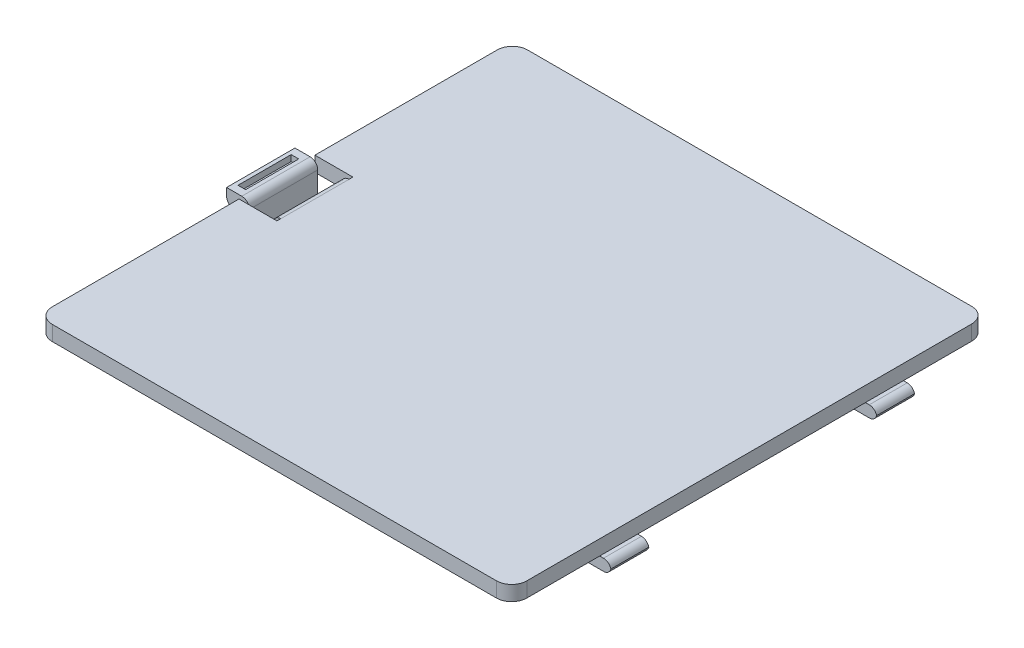
SolidWorks part; units mm, degrees
ref_plane "Front Plane" through (0, 0, 0) normal (0, 0, 1) x (1, 0, 0)
ref_plane "Top Plane" through (0, 0, 0) normal (0, 1, 0) x (1, 0, 0)
ref_plane "Right Plane" through (0, 0, 0) normal (1, 0, 0) x (0, 0, -1)
sketch "Sketch2" plane through (0, 0, 0) normal (0, 1, 0) x (1, 0, 0)
  line L0 (-98.1098, -87.5101) -> (50.4722, -87.5101)
  line L1 (-103.1898, -82.4301) -> (-103.1898, 66.3899)
  line L2 (-98.1098, 71.4699) -> (50.4722, 71.4699)
  line L3 (55.5522, -82.4301) -> (55.5522, 66.3899)
  arc A0 (-98.1098, -87.5101) -> (-103.1898, -82.4301) centre (-98.1098, -82.4301) cw
  arc A1 (50.4722, -87.5101) -> (55.5522, -82.4301) centre (50.4722, -82.4301) ccw
  arc A2 (50.4722, 71.4699) -> (55.5522, 66.3899) centre (50.4722, 66.3899) cw
  arc A3 (-103.1898, 66.3899) -> (-98.1098, 71.4699) centre (-98.1098, 66.3899) cw
  point P10 (55.5522, 71.4699)
  point P13 (-103.1898, 71.4699)
  dimension "D2" = 5.08
  dimension "D1" = 158.742
  dimension "D3" = 158.98
extrude "Boss-Extrude1" add sketch "Sketch2" along normal blind 5
sketch "Sketch8" plane through (0, 5, 0) normal (0, 1, 0) x (1, 0, 0)
  line L0 (-103.1898, 66.3899) -> (-103.1898, -82.4301) construction
  line L1 (-103.1898, 5.4299) -> (-90.4898, 5.4299)
  line L2 (-103.1898, 5.4299) -> (-103.1898, -19.9701)
  line L3 (-103.1898, -19.9701) -> (-90.4898, -19.9701)
  line L4 (-90.4898, 5.4299) -> (-90.4898, -19.9701)
  line L5 (50.4722, 71.4699) -> (-98.1098, 71.4699) construction
  dimension "D1" = 25.4
  dimension "D2" = 12.7
  dimension "D3" = 66.04
extrude "Cut-Extrude1" cut sketch "Sketch8" against normal blind 12.7
sketch "Sketch9" plane through (0, 0, 19.9701) normal (0, 0, -1) x (-1, 0, 0)
  line L0 (90.4898, 5) -> (90.4898, -9.5101)
  line L1 (93.0298, -12.0501) -> (100.9847, -12.0501)
  line L2 (103.5247, -9.5101) -> (103.5247, 5)
  line L3 (103.5247, 5) -> (100.9847, 5)
  line L4 (93.0298, 5) -> (93.0298, -6.9701)
  line L5 (95.5698, -9.5101) -> (98.4447, -9.5101)
  line L6 (100.9847, -6.9701) -> (100.9847, 5)
  line L7 (93.0298, 5) -> (90.4898, 5)
  arc A0 (90.4898, -9.5101) -> (93.0298, -12.0501) centre (93.0298, -9.5101) ccw
  arc A1 (100.9847, -12.0501) -> (103.5247, -9.5101) centre (100.9847, -9.5101) ccw
  arc A2 (98.4447, -9.5101) -> (100.9847, -6.9701) centre (98.4447, -6.9701) ccw
  arc A3 (93.0298, -6.9701) -> (95.5698, -9.5101) centre (95.5698, -6.9701) ccw
  dimension "D4" = 2.54
  dimension "D1" = 2.54
  dimension "D2" = 2.54
  dimension "D3" = 2.54
  dimension "D5" = 17.0501
extrude "Boss-Extrude6" add sketch "Sketch9" along normal blind 22.86 from offset 1.27
fillet "Fillet3" radius 2.54 1 edges at (-90.4898, 0, 7.2701)
sketch "Sketch12" plane through (-103.5247, 0, 0) normal (-1, 0, 0) x (0, 0, 1)
  line L0 (18.7001, 5) -> (18.7001, 0) construction
  line L1 (-4.1599, 5) -> (18.7001, 5)
  line L2 (-4.1599, 5) -> (-4.1599, -0.08)
  line L3 (-4.1599, -0.08) -> (18.7001, -0.08)
  line L4 (18.7001, 5) -> (18.7001, -0.08)
  dimension "D1" = 5.08
extrude "Boss-Extrude7" add sketch "Sketch12" along normal blind 5.08
fillet "Fillet8" radius 2.54 1 edges at (-100.9847, 5, 7.2701)
sketch "Sketch13" plane through (0, 5, 0) normal (0, 1, 0) x (1, 0, 0)
  line L0 (-108.6047, 4.1599) -> (-103.5247, 4.1599) construction
  line L1 (-104.7947, 1.6199) -> (-107.3347, 1.6199)
  line L2 (-104.7947, 1.6199) -> (-104.7947, -16.1601)
  line L3 (-104.7947, -16.1601) -> (-107.3347, -16.1601)
  line L4 (-107.3347, 1.6199) -> (-107.3347, -16.1601)
  line L5 (-108.6047, -18.7001) -> (-103.5247, -18.7001) construction
  line L6 (-103.5247, -18.7001) -> (-103.5247, 4.1599) construction
  line L8 (-108.6047, -18.7001) -> (-108.6047, 4.1599) construction
  dimension "D1" = 2.54
  dimension "D2" = 2.54
  dimension "D3" = 1.27
  dimension "D4" = 1.27
extrude "Cut-Extrude2" cut sketch "Sketch13" against normal blind 2.032
sketch "Sketch14" plane through (0, 0, -4.1599) normal (0, 0, -1) x (-1, 0, 0)
  line L0 (103.5247, -4.5768) -> (105.0487, -4.5768)
  line L1 (103.5247, -9.5101) -> (103.5247, -0.08) construction
  line L2 (105.0487, -4.5768) -> (103.5247, -7.3708)
  line L3 (103.5247, -7.3708) -> (103.5247, -4.5768)
  dimension "D1" = 1.524
  dimension "D2" = 2.794
extrude "Boss-Extrude8" add sketch "Sketch14" against normal up to surface (22.86 mm away) up to face at (-97.4306, -3.1874, 18.7001)
fillet "Fillet5" radius 2.54 1 edges at (-93.0298, 5, 7.2701)
fillet "Fillet6" radius 2.54 1 edges at (-108.6047, -0.08, 7.2701)
sketch "Sketch15" plane through (0, 0, -71.4699) normal (0, 0, -1) x (-1, 0, 0)
  line L4 (-85.2178, 2.5) -> (-23.3625, 2.5) construction
  line L6 (-59.3702, 0) -> (-49.2102, 0)
  line L7 (-59.3702, -3.81) -> (-59.3702, 0)
  line L8 (-49.2102, -3.81) -> (-59.3702, -3.81)
  line L9 (-49.2102, 0) -> (-49.2102, -3.81)
  point P8 (-54.2902, 2.5)
extrude "Boss-Extrude9" add sketch "Sketch15" against normal blind 12.7 from offset 27.94 offset against normal yes
extrude "Boss-Extrude10" add sketch "Sketch15<2>" against normal blind 12.7 from offset 116.84 offset against normal yes
sketch "Sketch15<2>" plane through (0, 0, -71.4699) normal (0, 0, -1) x (-1, 0, 0) same geometry as "Sketch15"
fillet "Fillet7" radius 2.54 6 edges at (59.3702, 0, 51.7201) (59.3702, -3.81, 51.7201) (49.2102, 0, 51.7201) (59.3702, -3.81, -37.1799) (59.3702, 0, -37.1799) (49.2102, 0, -37.1799)
